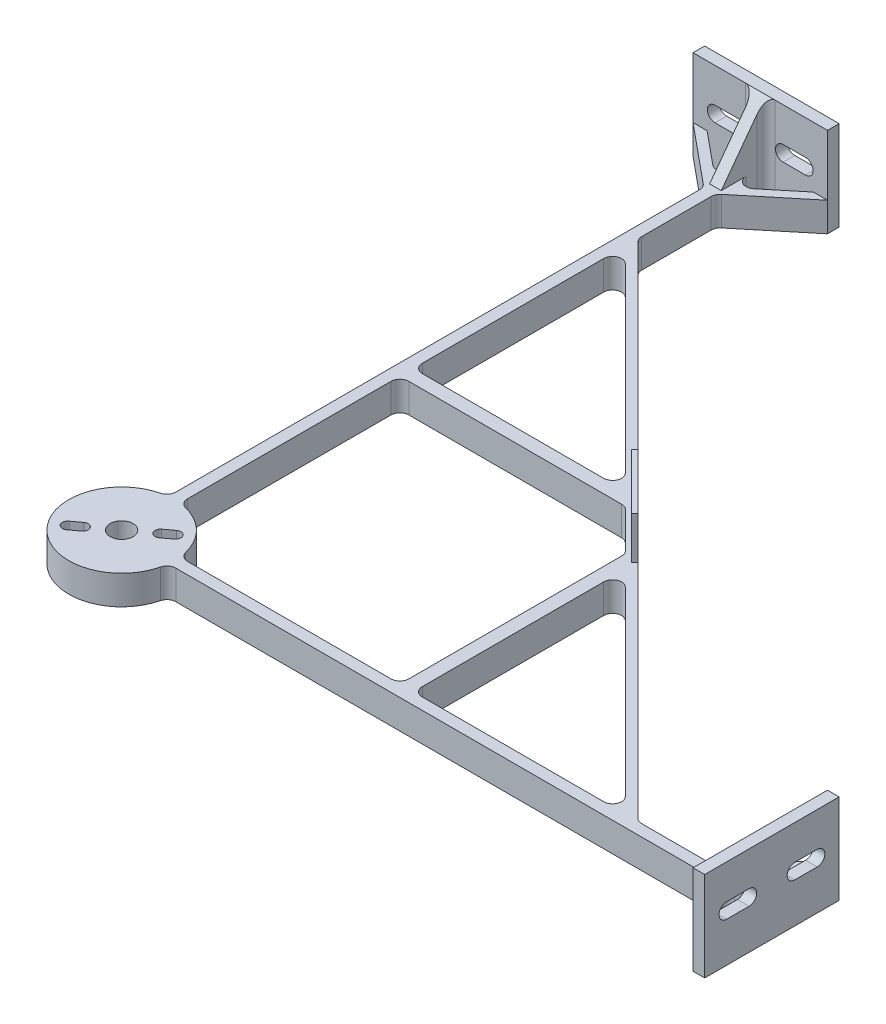
SolidWorks part; units mm, degrees
ref_plane "Front Plane" through (0, 0, 0) normal (0, 0, 1) x (1, 0, 0)
ref_plane "Top Plane" through (0, 0, 0) normal (0, 1, 0) x (1, 0, 0)
ref_plane "Right Plane" through (0, 0, 0) normal (1, 0, 0) x (0, 0, -1)
sketch "Sketch1" plane through (0, 0, 0) normal (0, 1, 0) x (1, 0, 0)
  line L0 (1.651, 14.8948) -> (1.651, 77.2021)
  line L1 (0, 0) -> (0, 189.2633) construction
  line L2 (-1.651, 14.8948) -> (-1.651, 180.975)
  line L3 (-1.651, 180.975) -> (1.651, 180.975)
  line L4 (-16.663, -12.33) -> (16.2408, 12.0176) construction
  line L5 (14.8948, -1.651) -> (180.975, -1.651)
  line L6 (6.3296, 4.6836) -> (8.7797, 6.4967) construction
  line L7 (5.4231, 5.9087) -> (7.8732, 7.7217)
  line L8 (180.975, -1.651) -> (180.975, 1.651)
  line L9 (14.8948, 1.651) -> (141.0789, 1.651)
  line L10 (7.2361, 3.4586) -> (9.6862, 5.2716)
  line L11 (0, 0) -> (12.0155, -16.238) construction
  line L12 (-6.3296, -4.6836) -> (-8.7797, -6.4967) construction
  line L13 (-7.2361, -3.4586) -> (-9.6862, -5.2716)
  line L14 (-5.4231, -5.9087) -> (-7.8732, -7.7217)
  line L15 (-1.651, 14.8948) -> (14.8948, -1.651) construction
  line L16 (1.651, 141.0789) -> (61.7178, 81.0121)
  line L17 (144.6711, 1.651) -> (1.651, 144.6711)
  line L18 (144.6711, 1.651) -> (166.629, 1.651)
  line L19 (141.0789, 1.651) -> (144.6711, 1.651) construction
  line L20 (1.651, 144.6711) -> (1.651, 180.975)
  line L21 (1.651, 81.0121) -> (61.7178, 81.0121)
  line L22 (1.651, 77.2021) -> (65.5278, 77.2021)
  line L23 (0, 0) -> (69.7604, 69.7604) construction
  line L24 (77.2021, 1.651) -> (77.2021, 65.5278)
  line L25 (81.0121, 1.651) -> (81.0121, 61.7178)
  line L26 (81.0121, 61.7178) -> (141.0789, 1.651)
  line L27 (65.5278, 77.2021) -> (77.2021, 65.5278)
  line L28 (1.651, 81.0121) -> (1.651, 141.0789)
  line L29 (169.921, 1.651) -> (180.975, 15.0573)
  line L30 (180.975, 15.0573) -> (180.975, 19.05)
  line L31 (180.975, 19.05) -> (166.629, 1.651)
  line L32 (166.4345, 0) -> (201.9953, 0) construction
  line L33 (180.975, -19.05) -> (166.629, -1.651)
  line L34 (180.975, -15.0573) -> (180.975, -19.05)
  line L35 (169.921, -1.651) -> (180.975, -15.0573)
  line L36 (169.921, 1.651) -> (180.975, 1.651)
  line L37 (166.629, 1.651) -> (169.921, 1.651) construction
  line L38 (-15.0573, 180.975) -> (-19.05, 180.975)
  line L39 (-19.05, 180.975) -> (-1.651, 166.629)
  line L40 (-1.651, 169.921) -> (-15.0573, 180.975)
  line L41 (1.651, 169.921) -> (15.0573, 180.975)
  line L42 (15.0573, 180.975) -> (19.05, 180.975)
  line L43 (19.05, 180.975) -> (1.651, 166.629)
  arc A0 (14.8948, 1.651) -> (1.651, 14.8948) centre (0, 0) ccw
  circle A1 centre (0, 0) radius 3.2385
  arc A2 (5.4231, 5.9087) -> (7.2361, 3.4586) centre (6.3296, 4.6836) ccw
  arc A3 (9.6862, 5.2716) -> (7.8732, 7.7217) centre (8.7797, 6.4967) ccw
  arc A4 (-7.2361, -3.4586) -> (-5.4231, -5.9087) centre (-6.3296, -4.6836) cw
  arc A5 (-7.8732, -7.7217) -> (-9.6862, -5.2716) centre (-8.7797, -6.4967) cw
  arc A6 (-1.651, 14.8948) -> (14.8948, -1.651) centre (0, 0) ccw
  point P14 (7.5546, 5.5901)
  point P25 (-7.5546, -5.5901)
  point P34 (142.875, 1.651)
  point P53 (168.275, 1.651)
  dimension "D3" = 29.972
  dimension "D1" = 6.477
  dimension "D6" = 1.524
  dimension "D7" = 3.048
  dimension "D2" = 53.5
  dimension "D4" = 3.302
  dimension "D5" = 3.302
  dimension "D8" = 7.874
  dimension "D9" = 2.54
  dimension "D10" = 38.1
  dimension "D11" = 3.81
  dimension "D12" = 16.51
  dimension "D13" = 38.1
  dimension "D14" = 12.7
  dimension "D15" = 2.54
  dimension "D16" = 180.975
  dimension "D17" = 180.975
extrude "Boss-Extrude1" add sketch "Sketch1" along normal blind 8.255 contours L2 A6 L5 L8 L36 L29 L30 L31 L18 L17 L20 L3 L14 A5 L13 A4 L9 A0 L0 L22 L27 L24 L25 L26 L21 L28 L16 A1 A3 L10 A2 L7 | L35 L5 L33 L34 | L2 L40 L38 L39 | L43 L42 L41 L20 region at (1.1203, 0, -90.7619) region at (-9.3955, 0, -174.5894) region at (174.5894, 0, 9.3955) region at (9.3955, 0, -174.5894)
sketch "Sketch3" plane through (0, 0, 0) normal (0, 1, 0) x (1, 0, 0)
  line L0 (0, 0) -> (128.7769, 128.7769) construction
  line L1 (180.975, 19.05) -> (184.277, 19.05)
  line L2 (180.975, 19.05) -> (180.975, -19.05)
  line L3 (180.975, -19.05) -> (184.277, -19.05)
  line L4 (184.277, 19.05) -> (184.277, -19.05)
  line L5 (19.05, 184.277) -> (-19.05, 184.277)
  line L6 (-19.05, 180.975) -> (-19.05, 184.277)
  line L7 (19.05, 180.975) -> (-19.05, 180.975)
  line L8 (19.05, 180.975) -> (19.05, 184.277)
  dimension "D1" = 3.302
extrude "Boss-Extrude3" add sketch "Sketch3" along normal blind 25.4
sketch "Sketch4" plane through (0, 8.255, 0) normal (0, 1, 0) x (1, 0, 0)
  line L0 (65.2584, 81.0637) -> (64.3604, 80.1656)
  line L1 (144.6711, 1.651) -> (1.651, 144.6711) construction
  line L2 (64.3604, 80.1656) -> (80.1656, 64.3604)
  line L3 (80.1656, 64.3604) -> (81.0637, 65.2584)
  line L4 (81.0637, 65.2584) -> (65.2584, 81.0637)
  line L5 (71.365, 71.365) -> (72.263, 72.263) construction
  line L6 (65.5278, 77.2021) -> (77.2021, 65.5278) construction
  dimension "D1" = 22.352
  dimension "D2" = 1.27
extrude "Boss-Extrude4" add sketch "Sketch4" along normal blind 11.938
sketch "Sketch5" plane through (184.277, 0, 0) normal (1, 0, 0) x (0, 0, -1)
  line L0 (-12.827, 13.4726) -> (-6.477, 13.4726) construction
  line L1 (-12.827, 15.6316) -> (-6.477, 15.6316)
  line L2 (-12.827, 11.3136) -> (-6.477, 11.3136)
  line L3 (0, 4.9298) -> (0, 30.0782) construction
  line L4 (12.827, 13.4726) -> (6.477, 13.4726) construction
  line L5 (12.827, 15.6316) -> (6.477, 15.6316)
  line L6 (12.827, 11.3136) -> (6.477, 11.3136)
  arc A0 (-12.827, 15.6316) -> (-12.827, 11.3136) centre (-12.827, 13.4726) ccw
  arc A1 (-6.477, 11.3136) -> (-6.477, 15.6316) centre (-6.477, 13.4726) ccw
  arc A2 (12.827, 15.6316) -> (12.827, 11.3136) centre (12.827, 13.4726) cw
  arc A3 (6.477, 11.3136) -> (6.477, 15.6316) centre (6.477, 13.4726) cw
  point P2 (-9.652, 13.4726)
  point P12 (9.652, 13.4726)
  dimension "D1" = 6.35
  dimension "D2" = 4.318
  dimension "D3" = 9.652
ref_plane "Plane1" through (0, 0, 0) normal (0.7071, 0, 0.7071) x (0.7071, 0, -0.7071)
extrude "Cut-Extrude1" cut sketch "Sketch5" against normal through all
mirror "Mirror1" about plane through (0, 0, 0) normal (0.7071, 0, 0.7071) of "Cut-Extrude1"
sketch "Sketch6" plane through (0, 0, 0) normal (0, 1, 0) x (1, 0, 0)
  line L0 (169.921, 1.651) -> (180.975, 1.651) construction
  line L1 (180.975, -1.651) -> (168.275, -1.651)
  line L2 (180.975, -1.651) -> (180.975, 1.651)
  line L3 (180.975, 1.651) -> (168.275, 1.651)
  line L4 (168.275, -1.651) -> (168.275, 1.651)
  dimension "D1" = 12.7
extrude "Boss-Extrude5" add sketch "Sketch6" along normal blind 25.4
sketch "Sketch7" plane through (0, 0, -1.651) normal (0, 0, -1) x (-1, 0, 0)
  line L0 (-180.975, 25.4) -> (-168.275, 8.255)
  line L1 (-168.275, 8.255) -> (-168.275, 25.4)
  line L2 (-168.275, 25.4) -> (-180.975, 25.4)
extrude "Cut-Extrude2" cut sketch "Sketch7" against normal blind 25.4
sketch "Sketch8" plane through (0, 0, 0) normal (0, 1, 0) x (1, 0, 0)
  line L0 (1.651, 169.921) -> (1.651, 180.975) construction
  line L1 (-1.651, 180.975) -> (1.651, 180.975)
  line L2 (-1.651, 180.975) -> (-1.651, 168.275)
  line L3 (-1.651, 168.275) -> (1.651, 168.275)
  line L4 (1.651, 180.975) -> (1.651, 168.275)
  dimension "D1" = 12.7
extrude "Boss-Extrude6" add sketch "Sketch8" along normal blind 25.4
sketch "Sketch9" plane through (1.651, 0, 0) normal (1, 0, 0) x (0, 0, -1)
  line L0 (180.975, 25.4) -> (168.275, 8.255)
  line L1 (168.275, 8.255) -> (168.275, 25.4)
  line L2 (168.275, 25.4) -> (180.975, 25.4)
extrude "Cut-Extrude3" cut sketch "Sketch9" against normal blind 25.4
fillet "Fillet1" radius 2.54 28 edges at (180.975, 12.7, 1.651) (-1.651, 12.7, -180.975) (141.0789, 4.1275, -1.651) (61.7178, 4.1275, -81.0121) (1.651, 4.1275, -141.0789) (81.0121, 4.1275, -61.7178) (14.8948, 4.1275, 1.651) (-1.651, 4.1275, -14.8948) (180.975, 12.7, -1.651) (77.2021, 4.1275, -1.651) (1.651, 12.7, -180.975) (1.651, 4.1275, -77.2021) (166.629, 4.1275, 1.651) (65.5278, 4.1275, -77.2021) (-1.651, 4.1275, -166.629) (77.2021, 4.1275, -65.5278) (1.651, 4.1275, -166.629) (1.651, 4.1275, -14.8948) (1.651, 4.1275, -144.6711) (1.651, 4.1275, -81.0121) (81.0121, 4.1275, -1.651) (166.629, 4.1275, -1.651) (14.8948, 4.1275, -1.651) (144.6711, 4.1275, -1.651) (-1.651, 4.1275, -169.921) (1.651, 4.1275, -169.921) (169.921, 4.1275, 1.651) (169.921, 4.1275, -1.651)
